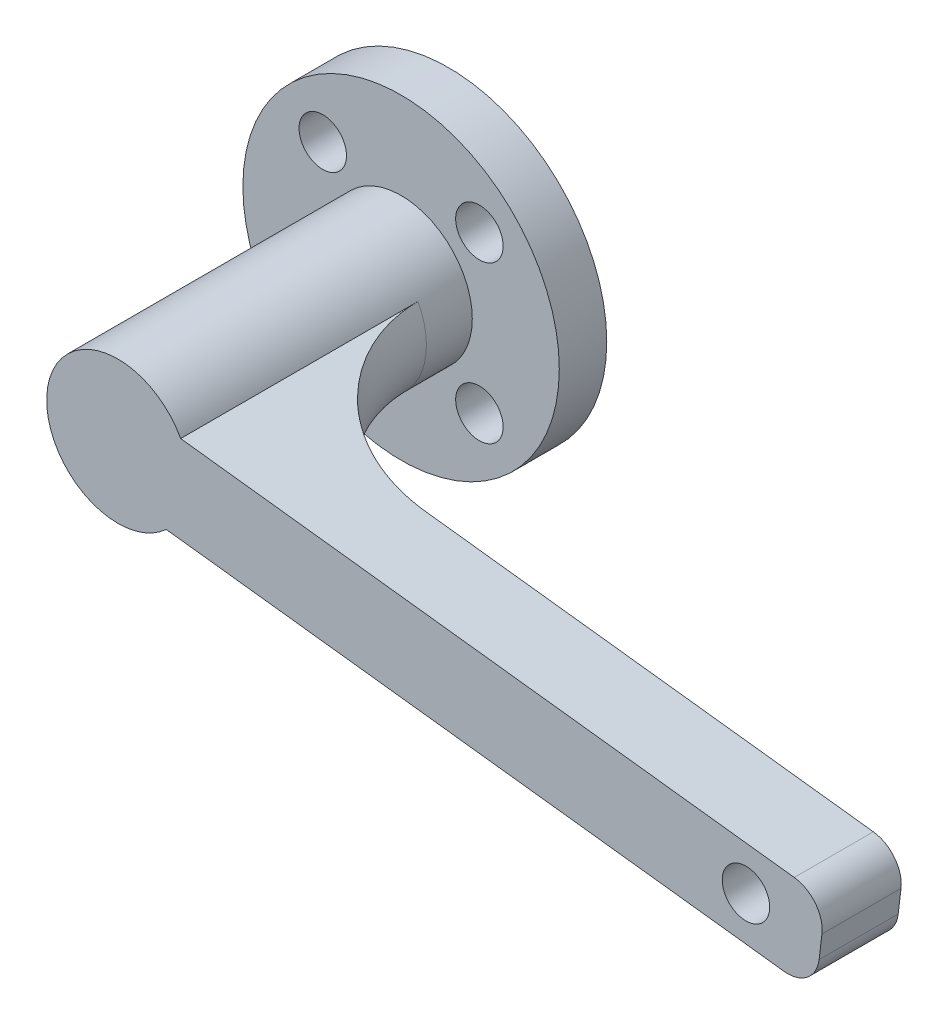
SolidWorks part; units mm, degrees
ref_plane "前视基准面" through (0, 0, 0) normal (0, 0, 1) x (1, 0, 0)
ref_plane "上视基准面" through (0, 0, 0) normal (0, 1, 0) x (1, 0, 0)
ref_plane "右视基准面" through (0, 0, 0) normal (1, 0, 0) x (0, 0, -1)
sketch "草图1" plane through (0, 0, 0) normal (0, 0, 1) x (1, 0, 0)
  circle A0 centre (0, 0) radius 10
  dimension "D1" = 20
extrude "凸台-拉伸1" add sketch "草图1" along normal blind 3
sketch "草图2" plane through (0, 0, 3) normal (0, 0, 1) x (1, 0, 0)
  line L1 (4.95, -4.95) -> (-4.95, -4.95)
  line L2 (4.95, -4.95) -> (4.95, 4.95)
  line L3 (4.95, 4.95) -> (-4.95, 4.95)
  line L4 (-4.95, -4.95) -> (-4.95, 4.95)
  line L5 (4.95, -4.95) -> (-4.95, 4.95) construction
  line L6 (4.95, 4.95) -> (-4.95, -4.95) construction
  circle A0 centre (0, 0) radius 1.5
  circle A2 centre (4.95, 4.95) radius 1.5
  circle A3 centre (-4.95, 4.95) radius 1.5
  circle A4 centre (-4.95, -4.95) radius 1.5
  circle A5 centre (4.95, -4.95) radius 1.5
  dimension "D1" = 3
  dimension "D2" = 9.9
  dimension "D4" = 3
  dimension "D3" = 9.9
extrude "切除-拉伸1" cut sketch "草图2" against normal through all contours L3 A3 L4 | L4 A3 L3 | L2 A2 L3 | L3 A2 L2 | L4 A4 L1 | L1 A4 L4 | L1 A5 L2 | L2 A5 L1 | A0 region at (-5.1622, -5.1622, 3) region at (-4.3134, -4.3134, 3) region at (4.3134, -4.3134, 3) region at (5.1622, -5.1622, 3) region at (-5.1622, 5.1622, 3) region at (-4.3134, 4.3134, 3) region at (4.3134, 4.3134, 3) region at (5.1622, 5.1622, 3)
sketch "草图3" plane through (0, 0, 3) normal (0, 0, 1) x (1, 0, 0)
  circle A0 centre (0, 0) radius 4.5
  circle A1 centre (-4.95, 4.95) radius 1.5 construction
  circle A2 centre (0, 0) radius 10
  circle A3 centre (0, 0) radius 10
  circle A4 centre (-4.95, 4.95) radius 1.5
  circle M5 centre (0, 0) radius 1.5
  dimension "D1" = 0
  dimension "D2" = 9
extrude "凸台-拉伸2" add sketch "草图3" along normal blind 12.9 contours A0 M5 region at (-4.3727, 0, 3)
sketch "草图4" plane through (0, 0, 0) normal (0, 0, -1) x (-1, 0, 0)
  circle A0 centre (0, 0) radius 1.5 construction
  circle A3 centre (0, 0) radius 1.5
extrude "凸台-拉伸4" add sketch "草图4" against normal up to surface (15.9 mm away) up to face at (1.5, 0, 15.9)
sketch "草图5" plane through (0, 0, 15.9) normal (0, 0, 1) x (1, 0, 0)
  line L0 (-0.2722, -0.1379) -> (44.4103, -5.4737) construction
  line L1 (44.7364, -2.7431) -> (44.0842, -8.2043)
  line L2 (44.0842, -8.2043) -> (-0.5983, -2.8685)
  line L3 (-0.5983, -2.8685) -> (0.0539, 2.5927)
  line L4 (44.7364, -2.7431) -> (0.0539, 2.5927)
  dimension "D1" = 45
  dimension "D2" = 2.75
extrude "凸台-拉伸5" add sketch "草图5" along normal blind 5
sketch "草图6" plane through (0, 0, 20.9) normal (0, 0, 1) x (1, 0, 0)
  line L0 (44.4103, -5.4737) -> (39.6974, -4.9109) construction
  line L1 (44.0842, -8.2043) -> (44.7364, -2.7431) construction
  line L2 (44.7364, -2.7431) -> (0.0539, 2.5927) construction
  circle A0 centre (39.6974, -4.9109) radius 1.5
  circle A1 centre (0, 0) radius 4.5 construction
  dimension "D1" = 3
  dimension "D2" = 40
extrude "切除-拉伸2" cut sketch "草图6" against normal through all
sketch "草图7" plane through (0, 0, 15.9) normal (0, 0, 1) x (1, 0, 0)
  line L3 (0.0539, 2.5927) -> (3.9664, 2.1255)
  line L4 (3.0544, -3.3047) -> (-0.5983, -2.8685)
  line L5 (-0.5983, -2.8685) -> (0.0539, 2.5927)
  line L6 (0.0539, 2.5927) -> (3.9664, 2.1255)
  line L7 (3.0544, -3.3047) -> (-0.5983, -2.8685)
  line L8 (-0.5983, -2.8685) -> (0.0539, 2.5927)
  arc A1 (3.9664, 2.1255) -> (3.0544, -3.3047) centre (0, 0) ccw
  arc A2 (3.9664, 2.1255) -> (3.0544, -3.3047) centre (0, 0) ccw
  dimension "D1" = 0
extrude "凸台-拉伸8" add sketch "草图7" along normal blind 5 contours L6 A2 L7 L8
fillet "圆角1" radius 10 1 edges at (4.4378, -0.7454, 15.9)
fillet "圆角2" radius 2 2 edges at (44.0842, -8.2043, 18.4) (44.7364, -2.7431, 18.4)
sketch "草图8" plane through (0, 0, 0) normal (0, 0, -1) x (-1, 0, 0)
  circle A0 centre (0, 0) radius 2.5
  dimension "D1" = 5
extrude "切除-拉伸3" cut sketch "草图8" against normal blind 3
